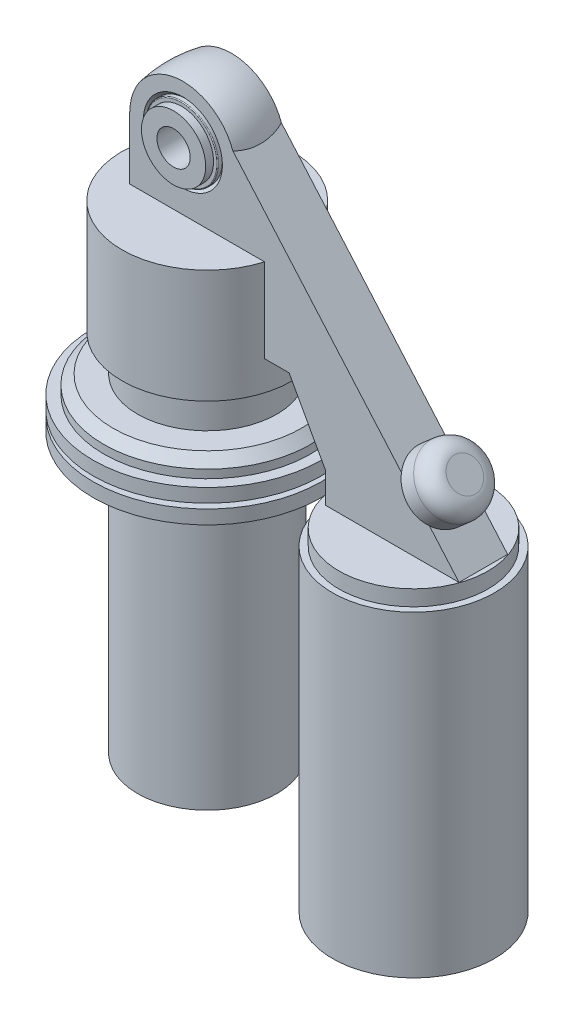
SolidWorks part; units mm, degrees
ref_plane "Front Plane" through (0, 0, 0) normal (0, 0, 1) x (1, 0, 0)
ref_plane "Top Plane" through (0, 0, 0) normal (0, 1, 0) x (1, 0, 0)
ref_plane "Right Plane" through (0, 0, 0) normal (1, 0, 0) x (0, 0, -1)
sketch "Sketch1" plane through (0, 0, 0) normal (0, 1, 0) x (1, 0, 0)
  line L0 (5, 10.0885) -> (5, -10.1115)
  line L1 (5, 10.0885) -> (9.65, 10.0885)
  line L2 (9.65, 10.0885) -> (9.65, 7.7207)
  line L3 (9.65, 7.7207) -> (10.6235, 7.7207)
  line L4 (10.8735, 7.4707) -> (10.8735, 6.3045)
  line L5 (11.8658, 7.2885) -> (10.8735, 6.3045)
  line L6 (0, 9.2654) -> (0, -9.2654) construction
  line L7 (-21.8629, -0.0115) -> (7.8575, -0.0115) construction
  line L8 (11.8658, 7.2885) -> (15.9282, 7.2885)
  line L9 (11.8658, -7.3115) -> (15.9282, -7.3115)
  line L10 (11.8658, -7.3115) -> (10.8735, -6.3275)
  line L11 (10.8735, -7.4937) -> (10.8735, -6.3275)
  line L12 (9.65, -7.7437) -> (10.6235, -7.7437)
  line L13 (9.65, -10.1115) -> (9.65, -7.7437)
  line L14 (5, -10.1115) -> (9.65, -10.1115)
  line L15 (9.65, 7.7207) -> (9.65, -0.0115) construction
  line L16 (9.65, -0.0115) -> (9.65, -7.7437) construction
  arc A0 (15.9282, 7.2885) -> (15.9282, -7.3115) centre (-23.4, -0.0115) cw
  arc A1 (10.8735, -7.4937) -> (10.6235, -7.7437) centre (10.6235, -7.4937) cw
  arc A2 (10.6235, 7.7207) -> (10.8735, 7.4707) centre (10.6235, 7.4707) cw
  point P2 (-4.3463, -0.0115)
  point P18 (16.6, -0.0115)
  point P20 (5, -0.0115)
  dimension "D5" = 0.25
  dimension "D6" = 16.6
  dimension "D7" = 40
  dimension "D1" = 20.2
  dimension "D2" = 10
  dimension "D3" = 19.3
  dimension "D4" = 14.6
revolve "Revolve1" add sketch "Sketch1"
sketch "Sketch2" plane through (0, 0, 0) normal (0, 0, 1) x (1, 0, 0)
  line L1 (0, 42.6805) -> (0, -22.2739) construction
  line L9 (-15, 0) -> (-16, 0)
  line L10 (-16, -44) -> (-16, 0)
  line L11 (-0.0718, -44) -> (-16, -44)
  line L12 (31.9282, -44) -> (-0.0718, -44)
  line L13 (42.9282, -64) -> (31.9282, -44)
  line L14 (42.9282, -73) -> (42.9282, -64)
  line L15 (83, -73) -> (42.9282, -73)
  line L16 (12.6886, 8) -> (83, -73)
  arc A4 (12.6886, 8) -> (-15, 0) centre (0, 0) cw
  dimension "D1" = 83
  dimension "D5" = 15
  dimension "D2" = 73
  dimension "D3" = 16
  dimension "D4" = 8
extrude "Extrude1" add sketch "Sketch2" along normal up to surface and the other way up to surface up to face at (-15.9282, 0, 7.3115) other way up to face at (-11.8658, 0, -7.2885)
sketch "Sketch5" plane through (0, 0, 0) normal (0, 0, 1) x (1, 0, 0)
  line L0 (-25.6, -18.8) -> (-25.6, -52.9)
  line L1 (-34.3, -69.2) -> (-31.1, -69.2)
  line L2 (0, 0) -> (0, -216.0086) construction
  line L3 (-25.6, -52.9) -> (-20.95, -52.9)
  line L4 (-20.95, -52.9) -> (-20.95, -63.9)
  line L5 (-31.1, -69.2) -> (-31.1, -66.7)
  line L6 (-34.3, -69.2) -> (-34.3, -73.3)
  line L7 (-34.3, -73.3) -> (-30.4, -73.3)
  line L8 (-20.95, -78.95) -> (-20.95, -162.65)
  line L9 (-20.95, -162.65) -> (0, -162.65)
  line L10 (0, -162.65) -> (0, -18.8)
  line L11 (-30.4, -73.3) -> (-30.4, -74.8)
  line L12 (-30.4, -74.8) -> (-34.3, -74.8)
  line L13 (-34.3, -74.8) -> (-34.3, -78.95)
  line L14 (-34.3, -78.95) -> (-20.95, -78.95)
  line L15 (-31.1, -66.7) -> (-28.3, -63.9)
  line L16 (-28.3, -63.9) -> (-20.95, -63.9)
  line L17 (-31.1, -66.7) -> (-15.7575, -66.7) construction
  line L18 (-25.6, -18.8) -> (0, -18.8)
  dimension "D1" = 34.3
  dimension "D2" = 15.05
  dimension "D3" = 18.8
  dimension "D4" = 25.6
  dimension "D5" = 11
  dimension "D6" = 78.95
  dimension "D7" = 4.15
  dimension "D8" = 1.5
  dimension "D9" = 4.1
  dimension "D10" = 2.5
  dimension "D11" = 62.2
  dimension "D12" = 60.8
  dimension "D13" = 83.7
  dimension "D14" = 41.9
  dimension "D15" = 45
revolve "Revolve2" add sketch "Sketch5" angle 360 about L2
sketch3d "3DSketch1"
  line L0 (0, -162.65, 0) -> (0, 22.4913, 0) construction
  line L1 (0, -162.65, 0) -> (0, -78.95, 0) construction
  line L2 (0, 0, 10.0885) -> (0, 0, -10.0885) construction
  line L3 (0, 0, 10.1115) -> (0, 0, -10.0885) construction
  line L4 (0, 0, 10.1115) -> (0, 0, 7.7437) construction
  point P10 (0, 0, 0)
sketch "Sketch6" plane through (0, 0, 0) normal (0, 0, 1) x (1, 0, 0)
  line L0 (62, -208.5399) -> (62, -21.7963) construction
  line L1 (86.35, -172.9) -> (86.35, -77.7)
  line L2 (86.35, -172.9) -> (84.3657, -172.9)
  line L3 (83.0117, -172.3094) -> (84.3657, -171.3768)
  line L4 (86.35, -77.7) -> (84.3903, -77.7)
  line L5 (62, -73) -> (62, -178.2241)
  line L6 (84.3903, -77.7) -> (84.3903, -73)
  line L7 (84.3657, -171.3768) -> (84.3657, -172.9)
  line L9 (83.0117, -172.3094) -> (81.1352, -172.3094)
  line L10 (81.1352, -172.3094) -> (79.985, -169.3982)
  line L11 (83, -73) -> (42.9282, -73) construction
  line L12 (79.985, -169.3982) -> (73.1488, -169.3982)
  line L13 (84.3903, -73) -> (62, -73)
  line L14 (73.1488, -169.3982) -> (71.7781, -173.1016)
  line L16 (71.7781, -173.1016) -> (70.3418, -173.1016)
  line L18 (70.3418, -173.1016) -> (70.3418, -176.5493)
  line L20 (70.3418, -176.5493) -> (68.7442, -176.5493)
  line L21 (68.7442, -176.5493) -> (67.4435, -178.2241)
  line L22 (67.4435, -178.2241) -> (62, -178.2241)
  line L23 (0, -162.65) -> (0, 22.4913) construction
  dimension "D1" = 77.7
  dimension "D2" = 95.2
  dimension "D3" = 62
  dimension "D4" = 48.7
revolve "Revolve3" add sketch "Sketch6" angle 360 about L0
ref_plane "Plane1" through (75, 0, 0) normal (1, 0, 0) x (0, 0, -1)
sketch "Sketch9" plane through (33.3518, -15.8044, 0) normal (0.7552, 0.6555, 0) x (0, 0, -1)
  line L0 (-7.3115, -75.7382) -> (7.2885, -75.7382) construction
  circle A0 centre (0, -55.7382) radius 9.73
  dimension "D1" = 20
extrude "Extrude2" add sketch "Sketch9" along normal blind 10
fillet "Fillet1" radius 5 1 edges at (71.063, -43.9934, 0) type face fillet first side face at (71.063, -43.9934, 0) second side face at (71.063, -43.9934, 0)
